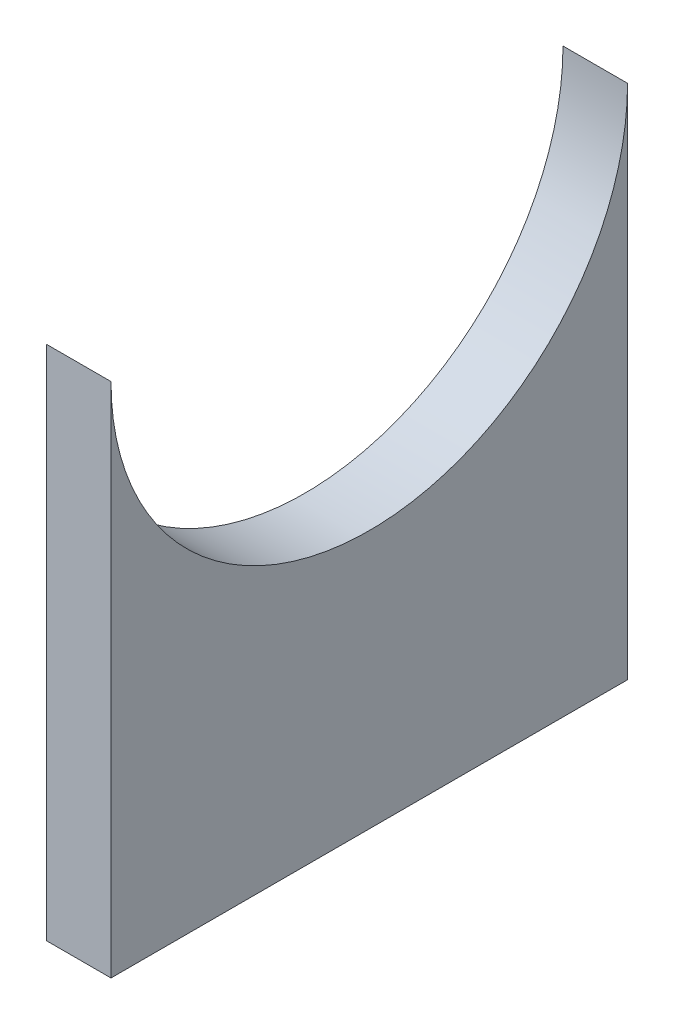
SolidWorks part; units mm, degrees
ref_plane "Front Plane" through (0, 0, 0) normal (0, 0, 1) x (1, 0, 0)
ref_plane "Top Plane" through (0, 0, 0) normal (0, 1, 0) x (1, 0, 0)
ref_plane "Right Plane" through (0, 0, 0) normal (1, 0, 0) x (0, 0, -1)
sketch "Sketch1" plane through (0, 0, 0) normal (1, 0, 0) x (0, 0, -1)
  line L1 (-12.7, -12.7) -> (12.7, -12.7)
  line L2 (-12.7, -12.7) -> (-12.7, 12.7)
  line L4 (12.7, -12.7) -> (12.7, 12.7)
  line L5 (-12.7, -12.7) -> (12.7, 12.7) construction
  line L6 (-12.7, 12.7) -> (12.7, -12.7) construction
  line L7 (-12.7, 12.7) -> (12.7, 12.7) construction
  arc A0 (-12.7, 12.7) -> (12.7, 12.7) centre (0, 12.7) ccw
  point P0 (0, 0)
  dimension "D1" = 25.4
  dimension "D3" = 25.4
extrude "Boss-Extrude1" add sketch "Sketch1" along normal blind 3.175
sketch "Sketch6" plane through (0, 0, 0) normal (-1, 0, 0) x (0, 0, 1)
  circle A0 centre (-8.8899, -4.309) radius 1.4732
